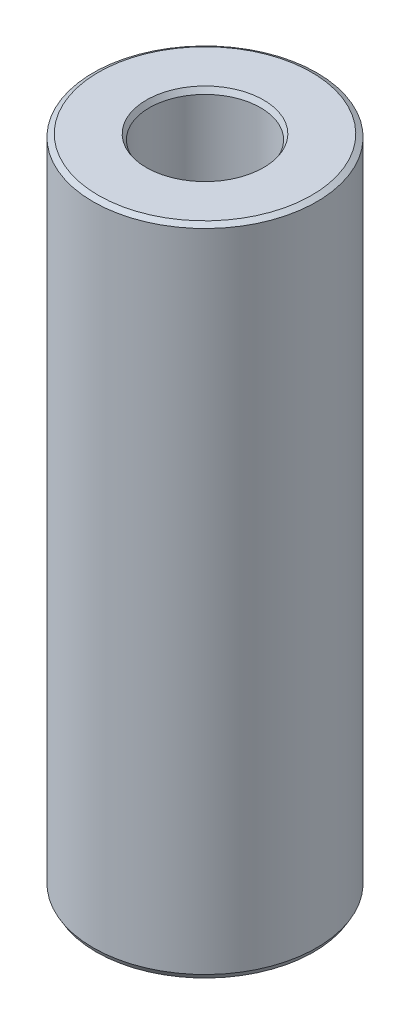
SolidWorks part; units mm, degrees
ref_plane "Front Plane" through (0, 0, 0) normal (0, 0, 1) x (1, 0, 0)
ref_plane "Top Plane" through (0, 0, 0) normal (0, 1, 0) x (1, 0, 0)
ref_plane "Right Plane" through (0, 0, 0) normal (1, 0, 0) x (0, 0, -1)
sketch "Sketch1" plane through (0, 0, 0) normal (0, 1, 0) x (1, 0, 0)
  circle A0 centre (0, 0) radius 47.5
  dimension "SLEEVE_OD" = 95
extrude "Boss-Extrude1" add sketch "Sketch1" along normal blind 277.9668
sketch "Sketch2" plane through (0, 0, 0) normal (0, 1, 0) x (1, 0, 0)
  circle A0 centre (0, 0) radius 23.6294
  dimension "BORE_D" = 47.2588
extrude "Cut-Extrude1" cut sketch "Sketch2" along normal through all
chamfer "Chamfer1" distance 1.2693 angle 60 4 edges at (0, 277.9668, 23.6294) (0, 0, 23.6294) (0, 0, 47.5) (0, 277.9668, 47.5) first distance on face at (0, 277.9668, 23.6294) first distance on face at (0, 0, 23.6294) first distance on face at (0, 277.9668, 47.5)
